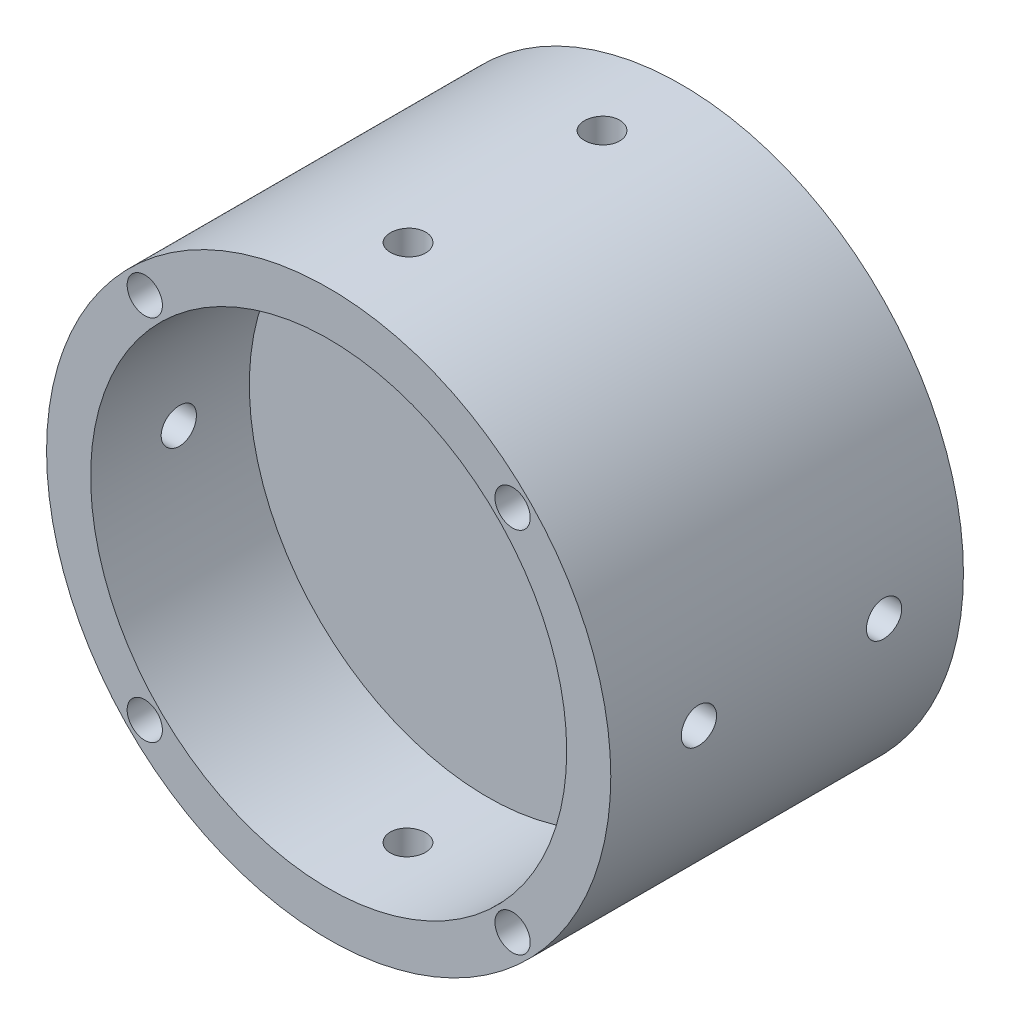
SolidWorks part; units mm, degrees
ref_plane "Front Plane" through (0, 0, 0) normal (0, 0, 1) x (1, 0, 0)
ref_plane "Top Plane" through (0, 0, 0) normal (0, 1, 0) x (1, 0, 0)
ref_plane "Right Plane" through (0, 0, 0) normal (1, 0, 0) x (0, 0, -1)
sketch "Sketch1" plane through (0, 0, 0) normal (0, 0, 1) x (1, 0, 0)
  circle A0 centre (0, 0) radius 80
extrude "Boss-Extrude1" add sketch "Sketch1" along normal blind 100
sketch "Sketch2" plane through (0, 0, 0) normal (0, 0, 1) x (1, 0, 0)
  circle A0 centre (0, 0) radius 67.5
ref_plane "Plane1" through (0, 0, 100) normal (0, 0, 1) x (1, 0, 0)
sketch "Sketch3" plane through (0, 0, 100) normal (0, 0, 1) x (1, 0, 0)
  circle A0 centre (0, 0) radius 67.5
extrude "Cut-Extrude1" cut sketch "Sketch3" against normal blind 45
extrude "Cut-Extrude5" cut sketch "Sketch2" along normal blind 45 contours A0
sketch "Sketch5" plane through (0, 0, 0) normal (1, 0, 0) x (0, 0, -1)
  line L0 (0, 0) -> (-22.5, 0)
  line L1 (-100, 0) -> (-75, 0)
  line L2 (-100, 80) -> (-100, -80) construction
  line L3 (-100, 0) -> (-75, 0)
  line L4 (-22.5, 0) -> (0, 0)
  circle A0 centre (-75, 0) radius 5
  circle A1 centre (-22.5, 0) radius 5
extrude "Cut-Extrude6" cut sketch "Sketch5" against normal blind 92 and the other way blind 106 contours A0
extrude "Cut-Extrude7" cut sketch "Sketch5<3>" against normal blind 120 and the other way blind 98 contours A1 | A0
sketch "Sketch5<3>" plane through (0, 0, 0) normal (1, 0, 0) x (0, 0, -1) same geometry as "Sketch5"
sketch "Sketch6" plane through (0, 0, 0) normal (0, 1, 0) x (1, 0, 0)
  line L0 (0, 0) -> (0, -22.5)
  line L1 (0, -100) -> (0, -77.5)
  line L2 (-88, -100) -> (88, -100) construction
  circle A0 centre (0, -22.5) radius 5
  circle A1 centre (0, -77.5) radius 5
extrude "Cut-Extrude8" cut sketch "Sketch6" against normal blind 146 and the other way blind 118 contours A0 | A1
sketch "Sketch7" plane through (0, 0, 0) normal (0, 0, 1) x (1, 0, 0)
  line L0 (0, 0) -> (-56.5685, 56.5685)
  line L1 (-56.5685, 56.5685) -> (-53.033, 53.033)
  line L2 (0, 0) -> (56.5685, 56.5685)
  line L3 (0, 0) -> (56.5685, -56.5685)
  line L4 (0, 0) -> (-56.5685, -56.5685)
  line L5 (-56.5685, 56.5685) -> (-52.1491, 52.1491)
  circle A0 centre (0, 0) radius 80 construction
  circle A1 centre (-52.1491, 52.1491) radius 5
  circle A2 centre (52.1491, 52.1491) radius 5
  circle A3 centre (52.1491, -52.1491) radius 5
  circle A4 centre (-52.1491, -52.1491) radius 5
  point P20 (0, 0)
  dimension "D1" = 4
extrude "Cut-Extrude15" cut sketch "Sketch7" along normal blind 118 contours A1 | A2 | A4 | A3
